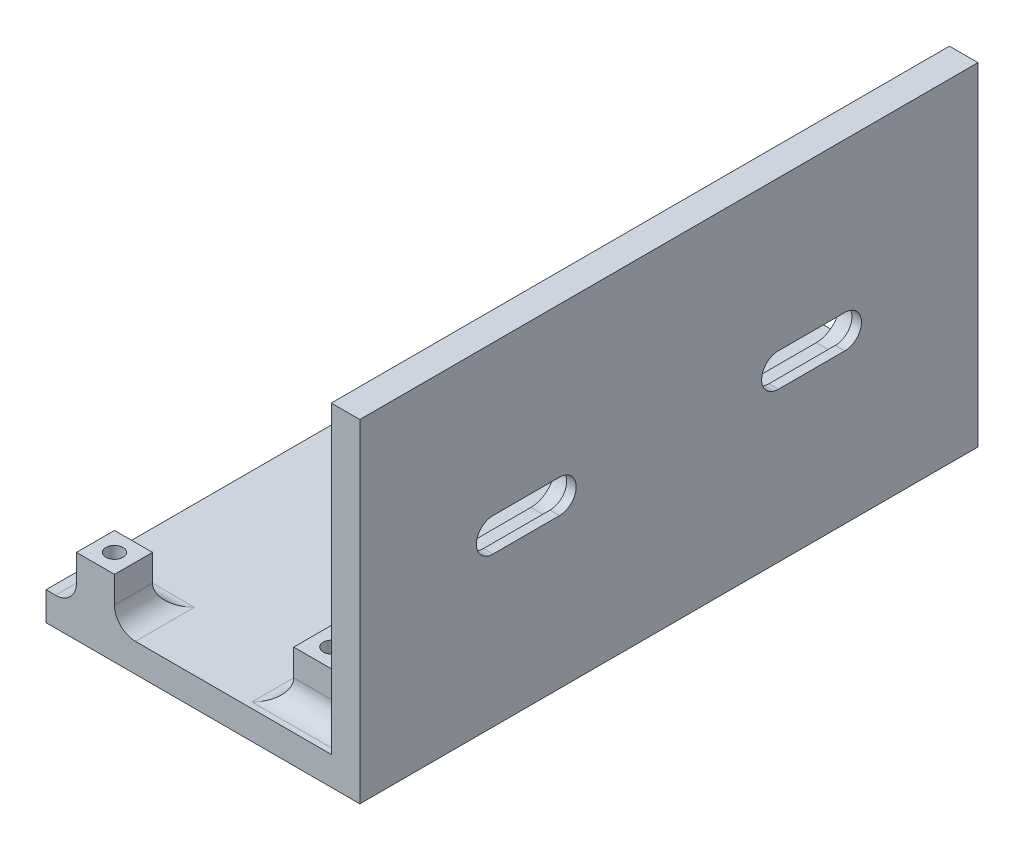
SolidWorks part; units mm, degrees
ref_plane "Front Plane" through (0, 0, 0) normal (0, 0, 1) x (1, 0, 0)
ref_plane "Top Plane" through (0, 0, 0) normal (0, 1, 0) x (1, 0, 0)
ref_plane "Right Plane" through (0, 0, 0) normal (1, 0, 0) x (0, 0, -1)
sketch "Sketch1" plane through (0, 0, 0) normal (0, 0, 1) x (1, 0, 0)
  line L0 (0, 0) -> (33, 0)
  line L1 (33, 0) -> (33, 35)
  line L2 (33, 35) -> (30, 35)
  line L3 (30, 35) -> (30, 3)
  line L4 (30, 3) -> (0, 3)
  line L5 (0, 3) -> (0, 0)
  dimension "D1" = 35
  dimension "D2" = 3
  dimension "D3" = 32
  dimension "D4" = 30
  dimension "D5" = 3
extrude "Boss-Extrude1" add sketch "Sketch1" along normal blind 65
sketch "Sketch2" plane through (0, 3, 0) normal (0, 1, 0) x (1, 0, 0)
  line L0 (0, -32.5) -> (30, -32.5)
  line L1 (0, -65) -> (0, 0) construction
  line L2 (30, -65) -> (30, 0) construction
  line L3 (15, -60.2) -> (15, -32.5)
  line L4 (15, -60.2) -> (25.25, -60.2)
  line L5 (27.25, -2.8) -> (23.25, -6.8) construction
  line L6 (27.25, -62.2) -> (23.25, -62.2)
  line L7 (27.25, -62.2) -> (27.25, -58.2)
  line L8 (27.25, -58.2) -> (23.25, -58.2)
  line L9 (23.25, -62.2) -> (23.25, -58.2)
  line L10 (27.25, -62.2) -> (23.25, -58.2) construction
  line L11 (27.25, -58.2) -> (23.25, -62.2) construction
  line L12 (27.25, -6.8) -> (23.25, -2.8) construction
  line L13 (27.25, -6.8) -> (23.25, -6.8)
  line L14 (23.25, -2.8) -> (23.25, -6.8)
  line L15 (27.25, -2.8) -> (23.25, -2.8)
  line L16 (27.25, -2.8) -> (27.25, -6.8)
  line L17 (15, -32.5) -> (15, -5.1)
  line L18 (15, -5.1) -> (6, -5.1)
  line L19 (15, -63) -> (5.2, -63)
  line L20 (8, -7.1) -> (4, -7.1)
  line L21 (8, -7.1) -> (8, -3.1)
  line L22 (8, -3.1) -> (4, -3.1)
  line L23 (4, -7.1) -> (4, -3.1)
  line L24 (8, -7.1) -> (4, -3.1) construction
  line L25 (8, -3.1) -> (4, -7.1) construction
  line L27 (7.2, -65) -> (3.2, -65)
  line L28 (7.2, -65) -> (7.2, -61)
  line L29 (7.2, -61) -> (3.2, -61)
  line L30 (3.2, -65) -> (3.2, -61)
  line L31 (7.2, -65) -> (3.2, -61) construction
  line L32 (7.2, -61) -> (3.2, -65) construction
  circle A0 centre (25.25, -60.2) radius 0.9
  circle A1 centre (25.25, -4.8) radius 0.9
  circle A2 centre (6, -5.1) radius 0.9
  circle A3 centre (5.2, -63) radius 0.9
  point P13 (25.25, -4.8)
  line M4 (30, -65) -> (30, 0)
  dimension "D5" = 1.8
  dimension "D10" = 1.8
  dimension "D15" = 1.8
  dimension "D2" = 10.25
  dimension "D3" = 4
  dimension "D4" = 4
  dimension "D6" = 27.4
  dimension "D7" = 9
  dimension "D8" = 4
  dimension "D9" = 4
  dimension "D11" = 9.8
  dimension "D12" = 30.5
  dimension "D13" = 4
  dimension "D14" = 4
  dimension "D16" = 27.7
extrude "Boss-Extrude2" add sketch "Sketch2" along normal blind 5 contours A0 L9 L6 L8 M4 | L15 L14 L13 A1 M4 | A3 L28 L29 L30 L27 | A2 L21 L22 L23 L20 region at (7.9434, 3, 6.1) region at (23.3066, 3, 59.2) region at (25.25, 3, 6.7434) region at (7.1434, 3, 64)
sketch "Sketch3" plane through (0, 3, 0) normal (0, 1, 0) x (1, 0, 0)
  line L0 (30, -32.5) -> (0, -32.5)
  line L1 (30, -65) -> (30, 0) construction
  line L2 (0, -65) -> (0, 0) construction
  line L3 (0, -32.5) -> (15, -32.5)
  line L4 (15, -32.5) -> (15, -17)
  line L5 (15, -17) -> (18.19, -17)
  line L6 (30, -22.8727) -> (30, -12.3727)
  line L8 (30, -22.8727) -> (13.5, -22.8727)
  line L9 (13.5, -22.8727) -> (13.5, -12.3727)
  line L10 (13.5, -12.3727) -> (30, -12.3727)
  dimension "D1" = 15.5
  dimension "D2" = 3.19
  dimension "D3" = 16.5
  dimension "D4" = 10.5
extrude "Cut-Extrude2" cut sketch "Sketch3" against normal up to next contours L10 L9 L8 region at (21.75, 3, 17.6227)
sketch "Sketch4" plane through (33, 0, 0) normal (1, 0, 0) x (0, 0, -1)
  line L0 (-32.5, 35) -> (-32.5, 0)
  line L1 (-65, 35) -> (0, 35) construction
  line L2 (-65, 0) -> (0, 0) construction
  line L3 (-32.5, 17.5) -> (-47.5, 17.5)
  line L4 (-44.0019, 17.5) -> (-50.9981, 17.5) construction
  line L5 (-44.0019, 15.75) -> (-50.9981, 15.75)
  line L6 (-44.0019, 19.25) -> (-50.9981, 19.25)
  line L7 (-20.9981, 17.5) -> (-14.0019, 17.5) construction
  line L8 (-20.9981, 15.75) -> (-14.0019, 15.75)
  line L9 (-20.9981, 19.25) -> (-14.0019, 19.25)
  arc A0 (-44.0019, 15.75) -> (-44.0019, 19.25) centre (-44.0019, 17.5) ccw
  arc A1 (-50.9981, 19.25) -> (-50.9981, 15.75) centre (-50.9981, 17.5) ccw
  arc A2 (-20.9981, 15.75) -> (-20.9981, 19.25) centre (-20.9981, 17.5) cw
  arc A3 (-14.0019, 19.25) -> (-14.0019, 15.75) centre (-14.0019, 17.5) cw
  point P11 (-47.5, 17.5)
  point P17 (-17.5, 17.5)
  dimension "D2" = 1.75
  dimension "D1" = 15
extrude "Cut-Extrude3" cut sketch "Sketch4" against normal up to next contours A3 L9 A2 L8 | L6 A1 L5 A0 region at (33, 15.8606, 47.5) region at (33, 17.5, 17.5)
sketch "Sketch5" plane through (30, 0, 0) normal (-1, 0, 0) x (0, 0, 1)
  line L0 (20.9981, 17.5) -> (14.0019, 17.5) construction
  line L1 (20.9981, 15) -> (14.0019, 15)
  line L2 (20.9981, 20) -> (14.0019, 20)
  line L3 (44.0019, 17.5) -> (50.9981, 17.5) construction
  line L4 (44.0019, 20) -> (50.9981, 20)
  line L5 (44.0019, 15) -> (50.9981, 15)
  arc A0 (20.9981, 15) -> (20.9981, 20) centre (20.9981, 17.5) ccw
  arc A1 (14.0019, 20) -> (14.0019, 15) centre (14.0019, 17.5) ccw
  arc A2 (44.0019, 20) -> (44.0019, 15) centre (44.0019, 17.5) ccw
  arc A3 (50.9981, 15) -> (50.9981, 20) centre (50.9981, 17.5) ccw
  point P4 (17.5, 17.5)
  point P9 (47.5, 17.5)
  dimension "D1" = 2.5
  dimension "D2" = 2.5
extrude "Cut-Extrude4" cut sketch "Sketch5" against normal blind 2
fillet "Fillet1" radius 2.2 15 edges at (27.25, 3, 60.2) (25.25, 3, 62.2) (25.25, 3, 58.2) (23.25, 3, 60.2) (7.2, 3, 63) (5.2, 3, 61) (3.2, 3, 63) (27.25, 3, 4.8) (25.25, 3, 6.8) (25.25, 3, 2.8) (23.25, 3, 4.8) (8, 3, 5.1) (6, 3, 7.1) (6, 3, 3.1) (4, 3, 5.1)
